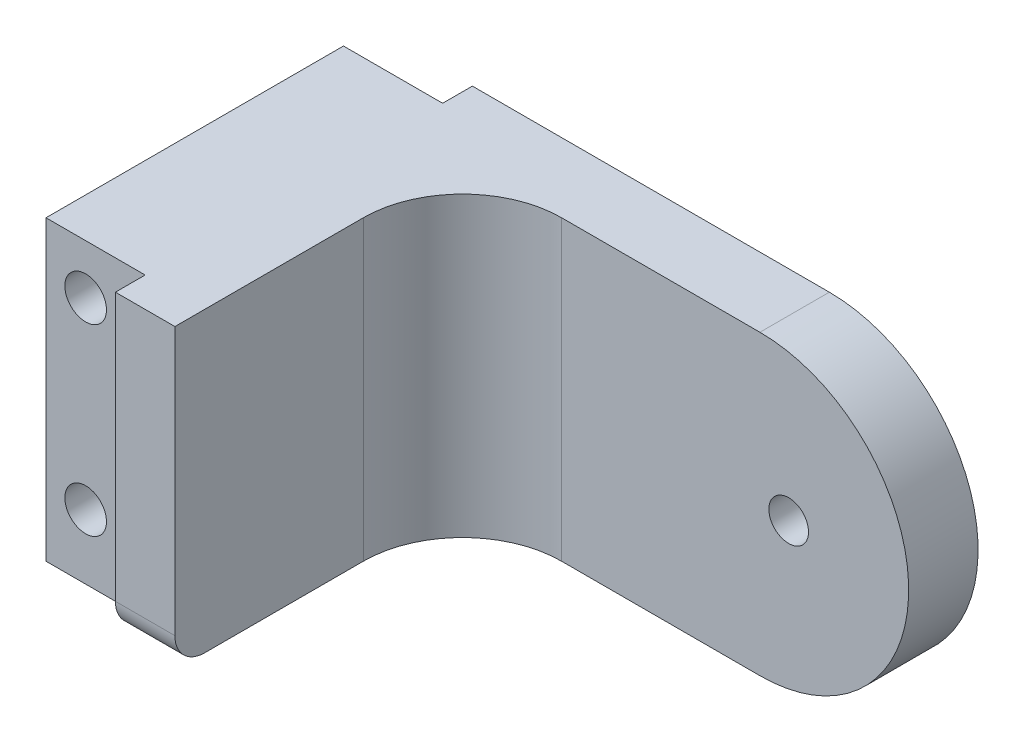
SolidWorks part; units mm, degrees
ref_plane "Front Plane" through (0, 0, 0) normal (0, 0, 1) x (1, 0, 0)
ref_plane "Top Plane" through (0, 0, 0) normal (0, 1, 0) x (1, 0, 0)
ref_plane "Right Plane" through (0, 0, 0) normal (1, 0, 0) x (0, 0, -1)
sketch "Sketch1" plane through (-52.7871, 0, 0.0004) normal (1, 0, 0) x (0, 0, -1)
  line L0 (33.0006, 215.1803) -> (3.0006, 215.18)
  line L3 (3.0006, 215.18) -> (3.0003, 245.18)
  line L4 (3.0003, 245.18) -> (0.0003, 245.18)
  line L5 (0.0003, 245.18) -> (0.0005, 218.18)
  line L8 (0.0003, 245.18) -> (0.0005, 218.18)
  line L9 (33.0003, 245.1803) -> (33.0006, 215.1803)
  line L10 (36.0005, 218.1803) -> (36.0003, 245.1803)
  line L11 (36.0003, 245.1803) -> (33.0003, 245.1803)
  line L13 (36.0005, 218.1803) -> (36.0003, 245.1803)
  line L14 (36.0003, 245.1803) -> (0.0003, 245.18)
  arc A1 (0.0005, 218.18) -> (3.0006, 215.18) centre (3.0005, 218.18) ccw
  arc A2 (0.0005, 218.18) -> (3.0006, 215.18) centre (3.0005, 218.18) ccw
  arc A3 (33.0006, 215.1803) -> (36.0005, 218.1803) centre (33.0005, 218.1803) ccw
  arc A4 (33.0006, 215.1803) -> (36.0005, 218.1803) centre (33.0005, 218.1803) ccw
  dimension "D1" = 0
  dimension "D2" = 0
extrude "Boss-Extrude1" add sketch "Sketch1" along normal blind 6
sketch "Sketch2" plane through (-46.7871, 0, 0.0004) normal (1, 0, 0) x (0, 0, -1)
  line L0 (29.0003, 245.1803) -> (29.0006, 215.1802)
  line L4 (3.0006, 215.18) -> (33.0006, 215.1803)
  line L5 (36.0005, 218.1803) -> (36.0003, 245.1803)
  line L6 (36.0003, 245.1803) -> (0.0003, 245.18)
  line L7 (0.0003, 245.18) -> (0.0005, 218.18)
  line L8 (29.0006, 215.1802) -> (33.0006, 215.1803)
  line L9 (36.0005, 218.1803) -> (36.0003, 245.1803)
  line L10 (36.0003, 245.1803) -> (29.0003, 245.1803)
  arc A2 (0.0005, 218.18) -> (3.0006, 215.18) centre (3.0005, 218.18) ccw
  arc A3 (33.0006, 215.1803) -> (36.0005, 218.1803) centre (33.0005, 218.1803) ccw
  arc A5 (33.0006, 215.1803) -> (36.0005, 218.1803) centre (33.0005, 218.1803) ccw
  dimension "D2" = 7
  dimension "D1" = 0
extrude "Boss-Extrude2" add sketch "Sketch2" along normal blind 45
sketch "Sketch3" plane through (-0.0003, 0.0003, -36.0024) normal (0, 0, -1) x (-1, 0, 0)
  line L0 (2.5959, 215.18) -> (2.5959, 245.18) construction
  line L1 (1.7871, 215.18) -> (52.7871, 215.18) construction
  line L2 (1.7871, 245.18) -> (52.7871, 245.18) construction
  line L3 (2.5959, 230.18) -> (52.7871, 230.18) construction
  line L4 (52.7871, 218.18) -> (52.7871, 245.18) construction
  line L5 (1.7871, 218.18) -> (1.7871, 245.18) construction
  line L6 (16.7871, 215.18) -> (-2.3545, 215.18)
  line L7 (-2.3545, 215.18) -> (-2.3545, 245.18)
  line L8 (-2.3545, 245.18) -> (16.7871, 245.18)
  arc A0 (16.7871, 245.18) -> (16.7871, 215.18) centre (16.7871, 230.18) ccw
extrude "Cut-Extrude1" cut sketch "Sketch3" against normal up to surface (7 mm away) up to face at (-24.2873, 230.1803, -29.0002)
sketch "Sketch4" plane through (-0.0003, 0.0003, -36.0024) normal (0, 0, -1) x (-1, 0, 0)
  line L0 (13.8885, 230.18) -> (13.8885, 247.0307) construction
  line L2 (1.7871, 230.18) -> (13.8885, 230.18) construction
  arc A0 (16.7871, 245.18) -> (7.7871, 218.18) centre (16.7871, 230.18) ccw construction
  circle A1 centre (13.8885, 230.18) radius 2
extrude "Cut-Extrude2" cut sketch "Sketch4" against normal through all
fillet "Fillet1" radius 10 1 edges at (-46.7873, 230.1803, -29)
sketch "Sketch5" plane through (-52.7871, 0, 0.0004) normal (-1, 0, 0) x (0, 0, 1)
  line L2 (-3.0003, 245.18) -> (-3.0003, 215.18)
  line L4 (-33.0006, 245.1803) -> (-33.0006, 215.1803)
  line L5 (-36.0003, 245.1803) -> (-0.0003, 245.18) construction
  line L6 (-33.0006, 245.1803) -> (-3.0003, 245.18)
  line L8 (-3.0006, 215.18) -> (-33.0006, 215.1803) construction
  line L9 (-3.0003, 215.18) -> (-33.0006, 215.1803)
extrude "Boss-Extrude3" add sketch "Sketch5" along normal up to surface (10 mm away)
sketch "Sketch6" plane through (-0.0003, 0, -33.0006) normal (0, 0, -1) x (-1, 0, 0)
  circle A0 centre (58.7873, 221.6803) radius 2.1
  circle A1 centre (58.7873, 221.6803) radius 2.1
  circle A2 centre (58.7873, 240.1806) radius 2.1
  circle A3 centre (58.7873, 240.1806) radius 2.1
  dimension "D1" = 0.5
  dimension "D2" = 0.5
extrude "Cut-Extrude3" cut sketch "Sketch6" against normal through all
